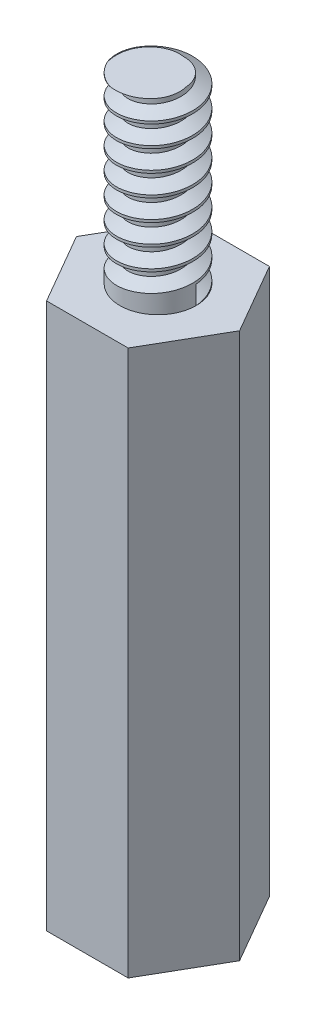
SolidWorks part; units mm, degrees
material "Brass"
ref_plane "Front Plane" through (0, 0, 0) normal (0, 0, 1) x (1, 0, 0)
ref_plane "Top Plane" through (0, 0, 0) normal (0, 1, 0) x (1, 0, 0)
ref_plane "Right Plane" through (0, 0, 0) normal (1, 0, 0) x (0, 0, -1)
sketch "Sketch1" plane through (0, 0, 0) normal (0, 1, 0) x (1, 0, 0)
  line L1 (1.3382, -2.3178) -> (2.6763, 0)
  line L2 (2.6763, 0) -> (1.3382, 2.3177)
  line L3 (1.3382, 2.3177) -> (-1.3382, 2.3178)
  line L4 (-1.3382, 2.3178) -> (-2.6763, 0)
  line L5 (-2.6763, 0) -> (-1.3382, -2.3177)
  line L6 (-1.3382, -2.3177) -> (1.3382, -2.3178)
  circle A0 centre (0, 0) radius 2.3178 construction
  dimension "D1" = 4.6355
extrude "Boss-Extrude1" add sketch "Sketch1" along normal blind 20
hole_wizard "CBORE for M2.5 Pan Head Machine Screw1" positions "Sketch2" profile "Sketch3" counterbore size "M2.5" standard "ANSI Metric"
sketch "Sketch2" plane through (0, 0, 0) normal (0, -1, 0) x (-1, 0, 0)
  point P0 (0, 0)
sketch "Sketch3" plane through (0, 0, 0) normal (1, 0, 0) x (0, 0, -1)
  line L0 (0, 0) -> (0, 12.8712)
  line L1 (0, 12.8712) -> (1.45, 12)
  line L2 (1.45, 12) -> (1.45, 2.1)
  line L3 (1.45, 2.1) -> (3, 2.1)
  line L4 (3, 2.1) -> (3, 0)
  line L5 (3, 0) -> (0, 0)
  line L10 (0, 12.8712) -> (-1.45, 12) construction
  line L11 (0, -6.35) -> (0, 107.95) construction
  dimension "Hole Dia." = 2.9
  dimension "Hole Depth" = 12
  dimension "C'Bore Dia." = 6
  dimension "C'Bore Depth" = 2.1
  dimension "Drill Angle" = 118
sketch "Sketch4" plane through (0, 20, 0) normal (0, 1, 0) x (1, 0, 0)
  circle A0 centre (0, 0) radius 1.25
  dimension "D1" = 2.5
extrude "Boss-Extrude2" add sketch "Sketch4" along normal blind 6
thread "Thread1" pitch 0.7 method cut profile "Thread Profile1" start angle 0, offset 0, length 10, pitch 0.7, diameter 2.5
ref_plane "Plane1" through (1.25, 20, 0) normal (0, 0, 1) x (1, 0, 0)
sketch "Thread Profile1" plane through (1.25, 20, 0) normal (0, 0, 1) x (1, 0, 0)
  line L0 (0, 0) -> (0, 0.7) construction
  line L11 (0, 0) -> (0, 0.6125)
  line L12 (0, 0.6125) -> (-0.3789, 0.3937)
  line L13 (-0.3789, 0.3937) -> (-0.3789, 0.2187)
  line L15 (-0.3789, 0.2187) -> (0, 0)
  line L17 (-0.3789, 0.3062) -> (0, 0.3062) construction
  point P2 (0, 0)
  dimension "Pitch" = 0.7
  dimension "Profile_Angle" = 60
  dimension "Profile_Land" = 0.175
  dimension "Profile_Height" = 0.3789
